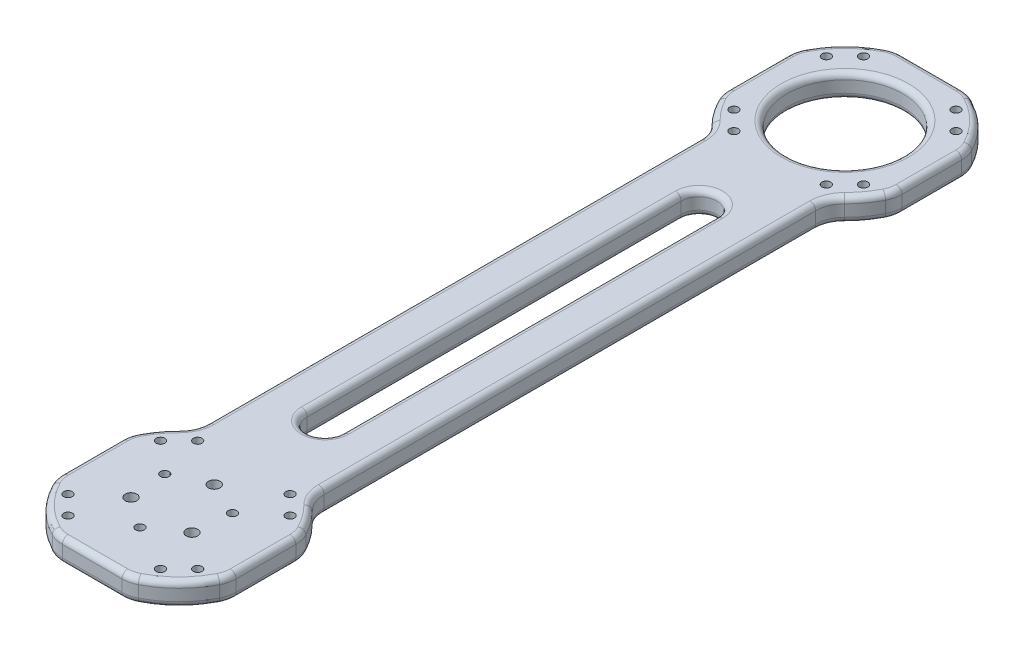
SolidWorks part; units mm, degrees
ref_plane "前视基准面" through (0, 0, 0) normal (0, 0, 1) x (1, 0, 0)
ref_plane "上视基准面" through (0, 0, 0) normal (0, 1, 0) x (1, 0, 0)
ref_plane "右视基准面" through (0, 0, 0) normal (1, 0, 0) x (0, 0, -1)
sketch "草图1" plane through (0, 0, 0) normal (0, 1, 0) x (1, 0, 0)
  line L0 (0, -31.6456) -> (0, -164.4547) construction
  line L1 (-30, 145) -> (30, 145) construction
  line L2 (-30, 145) -> (-30, -145) construction
  line L3 (-30, -145) -> (30, -145) construction
  line L4 (30, 145) -> (30, -145) construction
  line L5 (-30, 145) -> (30, -145) construction
  line L6 (-30, -145) -> (30, 145) construction
  line L7 (-30, -85) -> (30, -85) construction
  line L8 (-30, -85) -> (-30, -145) construction
  line L9 (-30, -145) -> (30, -145) construction
  line L10 (30, -85) -> (30, -145) construction
  line L11 (-30, -85) -> (30, -145) construction
  line L12 (-30, -145) -> (30, -85) construction
  line L13 (-20, -84.896) -> (-20, 84.896)
  line L14 (-30, -104.6922) -> (-30, -125.3078)
  line L15 (-10.3078, -145) -> (10.3078, -145)
  line L16 (30, -104.6922) -> (30, -125.3078)
  line L17 (20, -84.896) -> (20, 84.896)
  line L18 (0, 0) -> (75.3378, 0) construction
  line L19 (0, -115) -> (-15.9693, -92.6118) construction
  line L20 (15.9693, -92.6118) -> (0, -115) construction
  line L23 (-30, 145) -> (30, 85) construction
  line L24 (-30, 85) -> (30, 145) construction
  line L25 (30, 85) -> (30, 145) construction
  line L26 (-30, 145) -> (30, 145) construction
  line L27 (-30, 85) -> (-30, 145) construction
  line L28 (-30, 85) -> (30, 85) construction
  line L29 (-30, 145) -> (30, 145) construction
  line L30 (30, 104.6922) -> (30, 125.3078)
  line L31 (-10.3078, 145) -> (10.3078, 145)
  line L32 (-30, 104.6922) -> (-30, 125.3078)
  circle A0 centre (0, -115) radius 32.5 construction
  arc A1 (-22.9412, -91.9793) -> (-28.8889, -100.111) centre (0, -115) ccw
  arc A2 (-28.8889, -129.889) -> (-14.889, -143.8889) centre (0, -115) ccw
  arc A3 (14.889, -143.8889) -> (28.8889, -129.889) centre (0, -115) ccw
  arc A4 (22.9412, -91.9793) -> (28.8889, -100.111) centre (0, -115) cw
  circle A5 centre (0, -115) radius 27.5 construction
  circle A6 centre (-15.9693, -92.6118) radius 1.5
  circle A8 centre (15.9693, -92.6118) radius 1.5
  circle A9 centre (-22.3882, -130.9693) radius 1.5
  circle A10 centre (-22.3882, -99.0307) radius 1.5
  circle A11 centre (-15.9693, -137.3882) radius 1.5
  circle A12 centre (15.9693, -137.3882) radius 1.5
  circle A13 centre (22.3882, -130.9693) radius 1.5
  circle A14 centre (22.3882, -99.0307) radius 1.5
  arc A15 (20, -84.896) -> (22.9412, -91.9793) centre (30, -84.896) ccw
  arc A16 (30, -104.6922) -> (28.8889, -100.111) centre (20, -104.6922) ccw
  arc A17 (28.8889, -129.889) -> (30, -125.3078) centre (20, -125.3078) ccw
  arc A18 (10.3078, -145) -> (14.889, -143.8889) centre (10.3078, -135) ccw
  arc A19 (-14.889, -143.8889) -> (-10.3078, -145) centre (-10.3078, -135) ccw
  arc A20 (-30, -125.3078) -> (-28.8889, -129.889) centre (-20, -125.3078) ccw
  arc A21 (-28.8889, -100.111) -> (-30, -104.6922) centre (-20, -104.6922) ccw
  arc A22 (-20, -84.896) -> (-22.9412, -91.9793) centre (-30, -84.896) cw
  circle A23 centre (0, -115) radius 13.5 construction
  circle A24 centre (0, -115) radius 12.15 construction
  circle A25 centre (0, -102.85) radius 2
  circle A27 centre (10.5222, -121.075) radius 2
  circle A28 centre (-10.5222, -121.075) radius 2
  circle A29 centre (0, -128.5) radius 1.5
  circle A30 centre (-11.6913, -108.25) radius 1.5
  circle A31 centre (11.6913, -108.25) radius 1.5
  circle A34 centre (0, 115) radius 27.5 construction
  circle A35 centre (0, 115) radius 32.5 construction
  arc A42 (-20, 84.896) -> (-22.9412, 91.9793) centre (-30, 84.896) ccw
  arc A43 (-28.8889, 100.111) -> (-30, 104.6922) centre (-20, 104.6922) cw
  arc A44 (-30, 125.3078) -> (-28.8889, 129.889) centre (-20, 125.3078) cw
  arc A45 (-14.889, 143.8889) -> (-10.3078, 145) centre (-10.3078, 135) cw
  arc A46 (10.3078, 145) -> (14.889, 143.8889) centre (10.3078, 135) cw
  arc A47 (28.8889, 129.889) -> (30, 125.3078) centre (20, 125.3078) cw
  arc A48 (30, 104.6922) -> (28.8889, 100.111) centre (20, 104.6922) cw
  arc A49 (20, 84.896) -> (22.9412, 91.9793) centre (30, 84.896) cw
  circle A50 centre (22.3882, 99.0307) radius 1.5
  circle A51 centre (22.3882, 130.9693) radius 1.5
  circle A52 centre (15.9693, 137.3882) radius 1.5
  circle A53 centre (-15.9693, 137.3882) radius 1.5
  circle A54 centre (-22.3882, 99.0307) radius 1.5
  circle A55 centre (-22.3882, 130.9693) radius 1.5
  circle A56 centre (15.9693, 92.6118) radius 1.5
  circle A57 centre (-15.9693, 92.6118) radius 1.5
  arc A58 (22.9412, 91.9793) -> (28.8889, 100.111) centre (0, 115) ccw
  arc A59 (14.889, 143.8889) -> (28.8889, 129.889) centre (0, 115) cw
  arc A60 (-28.8889, 129.889) -> (-14.889, 143.8889) centre (0, 115) cw
  arc A61 (-22.9412, 91.9793) -> (-28.8889, 100.111) centre (0, 115) cw
  circle A62 centre (0, 115) radius 20
  point P0 (0, 0)
  point P6 (0, -115)
  point P48 (22.981, -92.019)
  point P51 (30, -102.5)
  point P54 (30, -127.5)
  point P57 (12.5, -145)
  point P60 (-12.5, -145)
  point P63 (-30, -127.5)
  point P66 (-30, -102.5)
  point P69 (-22.981, -92.019)
  point P80 (0, -115)
  point P83 (20, 0)
  point P88 (0, -115)
  point P89 (-20, 0)
  point P90 (0, 0)
  point P91 (-11.7021, -103.2686)
  point P98 (10.1617, -103.3395)
  point P99 (10.1601, -116.6629)
  point P100 (0, 0)
  point P101 (0, 0)
  point P102 (0, 0)
  point P103 (11.733, -103.3227)
  point P104 (9.9845, -116.9233)
  point P105 (-10.4894, -116.1315)
  point P146 (0, 115)
  point P147 (0, 115)
  point P148 (-22.981, 92.019)
  point P149 (-30, 102.5)
  point P150 (-30, 127.5)
  point P151 (-12.5, 145)
  point P152 (12.5, 145)
  point P153 (30, 127.5)
  point P154 (30, 102.5)
  point P155 (22.981, 92.019)
  point P156 (0, 115)
  dimension "D2" = 65
  dimension "D3" = 3
  dimension "D6" = 10
  dimension "D7" = 27
  dimension "D8" = 24.3
  dimension "D10" = 4
  dimension "D12" = 3
  dimension "D13" = 40
  dimension "D15" = 55
  dimension "D1" = 60
  dimension "D4" = 35.5
  dimension "D5" = 35.5
  dimension "D14" = 230
  dimension "D16" = 40
  dimension "D17" = 20
  dimension "D9" = 3
  dimension "D11" = 3
extrude "凸台-拉伸1" add sketch "草图1" along normal blind 8
fillet "圆角1" radius 2 34 edges at (-20.7645, 8, -88.7308) (-26.232, 8, -95.8133) (-29.7183, 8, -102.3352) (-30, 8, -115) (-29.7183, 8, -127.6648) (-22.981, 8, -137.981) (-12.6648, 8, -144.7183) (0, 8, -145) (12.6648, 8, -144.7183) (22.981, 8, -137.981) (29.7183, 8, -127.6648) (30, 8, -115) (29.7183, 8, -102.3352) (26.232, 8, -95.8133) (20.7645, 8, -88.7308) (20, 8, 0) (20.7645, 8, 88.7308) (26.232, 8, 95.8133) (29.7183, 8, 102.3352) (30, 8, 115) (29.7183, 8, 127.6648) (22.981, 8, 137.981) (12.6648, 8, 144.7183) (0, 8, 145) (-12.6648, 8, 144.7183) (-22.981, 8, 137.981) (-29.7183, 8, 127.6648) (-30, 8, 115) (-29.7183, 8, 102.3352) (-26.232, 8, 95.8133) (-20.7645, 8, 88.7308) (-20, 8, 0) (0, 8, -95) (0, 0, -95)
sketch "草图2" plane through (0, 0, 0) normal (0, -1, 0) x (1, 0, 0)
  line L0 (0, 64.6005) -> (0, -64.6005) construction
  line L1 (6.1519, 64.6005) -> (6.1519, -64.6005)
  line L2 (-6.1519, 64.6005) -> (-6.1519, -64.6005)
  arc A0 (6.1519, 64.6005) -> (-6.1519, 64.6005) centre (0, 64.6005) ccw
  arc A1 (-6.1519, -64.6005) -> (6.1519, -64.6005) centre (0, -64.6005) ccw
  point P2 (0, 0)
  point P8 (0, 45.9438)
  point P9 (0, 57.6654)
  point P10 (0, -64.6005)
extrude "切除-拉伸1" cut sketch "草图2" against normal blind 21.5 and the other way blind 18
fillet "圆角2" radius 2 40 edges at (0, 8, -70.7524) (-6.1519, 8, 0) (0, 8, 70.7524) (0, 0, -70.7524) (-6.1519, 0, 0) (0, 0, 70.7524) (-20.7645, 0, -88.7308) (-26.232, 0, -95.8133) (-29.7183, 0, -102.3352) (-30, 0, -115) (-29.7183, 0, -127.6648) (-22.981, 0, -137.981) (-12.6648, 0, -144.7183) (0, 0, -145) (12.6648, 0, -144.7183) (22.981, 0, -137.981) (29.7183, 0, -127.6648) (30, 0, -115) (29.7183, 0, -102.3352) (26.232, 0, -95.8133) (20.7645, 0, -88.7308) (20, 0, 0) (20.7645, 0, 88.7308) (26.232, 0, 95.8133) (29.7183, 0, 102.3352) (30, 0, 115) (29.7183, 0, 127.6648) (22.981, 0, 137.981) (12.6648, 0, 144.7183) (0, 0, 145) (-12.6648, 0, 144.7183) (-22.981, 0, 137.981) (-29.7183, 0, 127.6648) (-30, 0, 115) (-29.7183, 0, 102.3352) (-26.232, 0, 95.8133) (-20.7645, 0, 88.7308) (6.1519, 8, 0) (6.1519, 0, 0) (-20, 0, 0)
